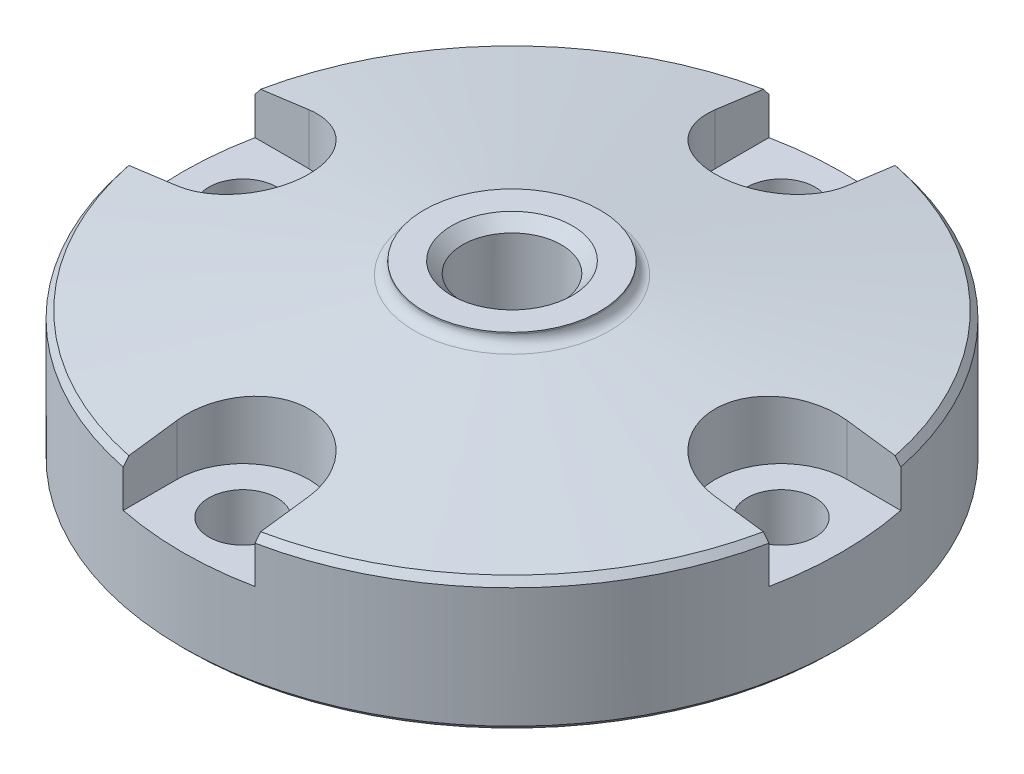
SolidWorks part; units mm, degrees
ref_plane "Спереди" through (0, 0, 0) normal (0, 0, 1) x (1, 0, 0)
ref_plane "Сверху" through (0, 0, 0) normal (0, 1, 0) x (1, 0, 0)
ref_plane "Справа" through (0, 0, 0) normal (1, 0, 0) x (0, 0, -1)
sketch "Эскиз1" plane through (0, 0, 0) normal (0, 1, 0) x (1, 0, 0)
  circle A0 centre (0, 0) radius 15
  dimension "D1" = 30
extrude "Цилиндр" add sketch "Эскиз1" along normal blind 8
sketch "Эскиз2" plane through (0, 0, 0) normal (0, 0, 1) x (1, 0, 0)
  line L0 (0, -1.5979) -> (0, 14.732) construction
  line L1 (4, 8) -> (15, 8)
  line L2 (15, 8) -> (-15, 8) construction
  line L3 (15, 8) -> (15, 6)
  line L4 (15, 0) -> (15, 8) construction
  line L5 (15, 6) -> (4, 7.5)
  line L6 (4, 7.5) -> (4, 8)
  dimension "D1" = 4
  dimension "D2" = 6
  dimension "D3" = 0.5
revolve "Вырез-Повернуть1" cut sketch "Эскиз2" angle 360 about L0
sketch "Эскиз3" plane through (0, 0, 0) normal (0, -1, 0) x (-1, 0, 0)
  circle A0 centre (0, 0) radius 10
  dimension "D1" = 20
extrude "Вырез-Вытянуть1" cut sketch "Эскиз3" against normal blind 2.5
sketch "Эскиз5" plane through (0, 2.5, 0) normal (0, -1, 0) x (1, 0, 0)
  circle A0 centre (0, 0) radius 9
  dimension "D1" = 18
extrude "Вырез-Вытянуть3" cut sketch "Эскиз5" against normal blind 1
sketch "Эскиз6" plane through (0, 3.5, 0) normal (0, -1, 0) x (1, 0, 0)
  circle A1 centre (0, 0) radius 4
  circle A2 centre (0, 0) radius 4
  dimension "D1" = 0
extrude "Бобышка-Вытянуть2" add sketch "Эскиз6" along normal blind 1.5
sketch "Эскиз7" plane through (0, 8, 0) normal (0, 1, 0) x (1, 0, 0)
  circle A0 centre (0, 0) radius 2.25
  dimension "D1" = 4.5
extrude "Вырез-Вытянуть4" cut sketch "Эскиз7" against normal through all
cosmetic thread "Условное изображение резьбы1" parameters "D2"=6
chamfer "Фаска3" distance 0.5 angle 45 1 edges at (0, 8, 2.25)
chamfer "Фаска4" distance 0.25 angle 45 1 edges at (0, 6, -15) first distance on face at (0, 6, -15)
chamfer "Фаска5" distance 0.25 angle 45 1 edges at (0, 0, 15)
fillet "Скругление1" radius 0.5 1 edges at (0, 7.5, -4)
sketch "Эскиз8" plane through (0, 0, 0) normal (0, 1, 0) x (1, 0, 0)
  line L0 (0, 0) -> (0, 16.9847) construction
  line L1 (5.3444, 15) -> (-11.095, 15) construction
  line L4 (3, 12.25) -> (3, 14.6969)
  line L5 (-3, 12.25) -> (-3, 14.6969)
  circle A0 centre (0, 0) radius 15 construction
  arc A2 (3, 14.6969) -> (-3, 14.6969) centre (0, 0) ccw
  arc A3 (3, 12.25) -> (-3, 12.25) centre (0, 12.25) cw
  dimension "D1" = 3
  dimension "D2" = 2.75
extrude "Вырез-Вытянуть6" cut sketch "Эскиз8" along normal through all from offset 4
sketch "Эскиз9" plane through (0, 4, 0) normal (0, 1, 0) x (1, 0, 0)
  circle A0 centre (0, 12.25) radius 1.55
  arc A1 (-3, 12.25) -> (3, 12.25) centre (0, 12.25) ccw construction
  dimension "D1" = 3.1
extrude "Вырез-Вытянуть7" cut sketch "Эскиз9" against normal through all
pattern_circular "Круговой массив1" count 4 over 360 about axis through (0, 5.7078, 0) along (0, -1, 0) of "Вырез-Вытянуть6", "Вырез-Вытянуть7"
